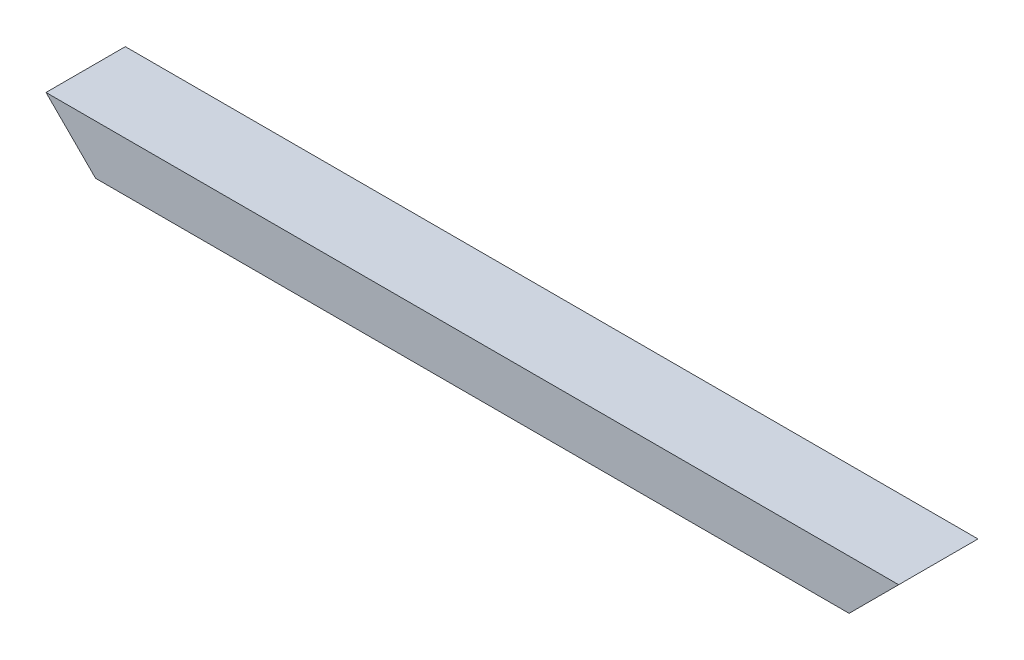
SolidWorks part; units mm, degrees
material "1023 Carbon Steel Sheet (SS)"
ref_plane "Front Plane" through (0, 0, 0) normal (0, 0, 1) x (1, 0, 0)
ref_plane "Top Plane" through (0, 0, 0) normal (0, 1, 0) x (1, 0, 0)
ref_plane "Right Plane" through (0, 0, 0) normal (1, 0, 0) x (0, 0, -1)
sketch "Sketch2" plane through (0, 0, 0) normal (0, 0, 1) x (1, 0, 0)
  line L0 (0, 0) -> (965.2, 0)
  line L1 (965.2, 0) -> (1028.7, 63.5)
  line L2 (1028.7, 63.5) -> (-63.5, 63.5)
  line L3 (-63.5, 63.5) -> (0, 0)
  dimension "D1" = 135
  dimension "D2" = 135
  dimension "D3" = 965.2
  dimension "D4" = 63.5
extrude "Boss-Extrude1" add sketch "Sketch2" along normal blind 101.6
